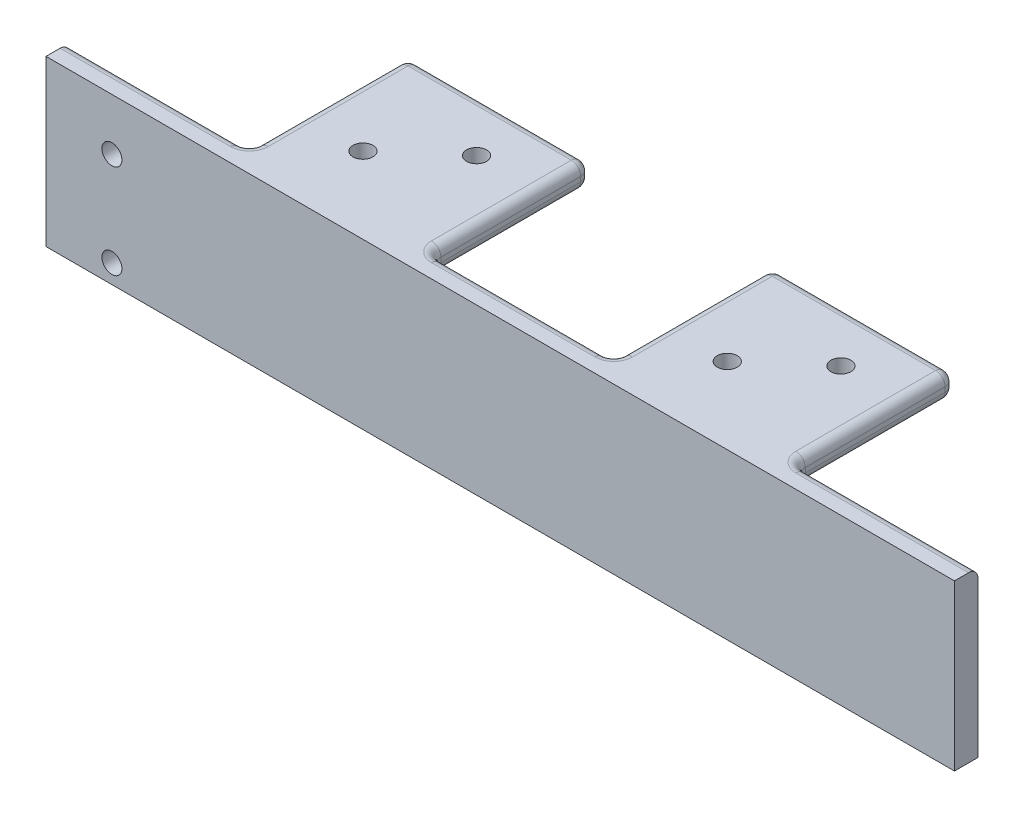
SolidWorks part; units mm, degrees
ref_plane "Front Plane" through (0, 0, 0) normal (0, 0, 1) x (1, 0, 0)
ref_plane "Top Plane" through (0, 0, 0) normal (0, 1, 0) x (1, 0, 0)
ref_plane "Right Plane" through (0, 0, 0) normal (1, 0, 0) x (0, 0, -1)
sketch "Sketch1" plane through (0, 0, 0) normal (0, 1, 0) x (1, 0, 0)
  line L1 (-96.5, 2.5) -> (96.5, 2.5)
  line L2 (-96.5, 2.5) -> (-96.5, -2.5)
  line L3 (-96.5, -2.5) -> (96.5, -2.5)
  line L4 (96.5, 2.5) -> (96.5, -2.5)
  line L5 (-96.5, 2.5) -> (96.5, -2.5) construction
  line L6 (-96.5, -2.5) -> (96.5, 2.5) construction
  point P0 (0, 0)
  dimension "D1" = 193
  dimension "D2" = 5
extrude "Boss-Extrude1" add sketch "Sketch1" along normal mid plane 30
sketch "Sketch2" plane through (0, 15, 0) normal (0, 1, 0) x (1, 0, 0)
  line L45 (96.5, 2.5) -> (-96.5, 2.5) construction
  line L46 (-58.3, 2.5) -> (-19.6, 2.5)
  line L47 (-58.3, 2.5) -> (-58.3, 36.2)
  line L48 (-58.3, 36.2) -> (-19.6, 36.2)
  line L49 (-19.6, 2.5) -> (-19.6, 36.2)
  line L51 (19.1, 36.2) -> (57.8, 36.2)
  line L52 (19.1, 2.5) -> (19.1, 36.2)
  line L53 (19.1, 2.5) -> (57.8, 2.5)
  line L54 (57.8, 2.5) -> (57.8, 36.2)
  line L55 (-58.3, 36.2) -> (-19.6, 36.2) construction
  line L60 (96.5, -2.5) -> (96.5, 2.5) construction
  dimension "D1" = 38.7
  dimension "D2" = 33.7
  dimension "D4" = 38.7
  dimension "D5" = 2
  dimension "D3" = 38.7
extrude "Boss-Extrude2" add sketch "Sketch2" along normal blind 5
sketch "Sketch3" plane through (0, 15, 0) normal (0, -1, 0) x (1, 0, 0)
  line L0 (-45.4, -13.73) -> (32, -13.73) construction
  line L4 (-19.6, -2.5) -> (-19.6, -36.2) construction
  line L6 (-19.6, -2.5) -> (-58.3, -2.5) construction
  line L7 (-58.3, -36.2) -> (-19.6, -36.2) construction
  circle A4 centre (-45.4, -13.73) radius 2.125
  circle A5 centre (-32.5, -24.97) radius 2.125
  circle A20 centre (32, -13.73) radius 2.125
  circle A21 centre (44.9, -24.97) radius 2.125
  dimension "D1" = 11.23
  dimension "D2" = 4.25
  dimension "D3" = 4.25
  dimension "D4" = 12.9
  dimension "D5" = 11.23
  dimension "D6" = 77.4
  dimension "D8" = 12.9
extrude "Cut-Extrude1" cut sketch "Sketch3" against normal up to next
fillet "Fillet3" radius 2 8 edges at (-19.6, 17.5, -2.5) (-58.3, 17.5, -2.5) (-58.3, 17.5, -36.2) (-19.6, 17.5, -36.2) (19.1, 17.5, -2.5) (19.1, 17.5, -36.2) (57.8, 17.5, -36.2) (57.8, 17.5, -2.5)
fillet "Fillet4" radius 2 31 edges at (-19.0142, 20, -3.0858) (-19.0142, 15, -3.0858) (-58.8858, 20, -3.0858) (-58.8858, 15, -3.0858) (-58.3, 15, -19.35) (-58.3, 20, -19.35) (-57.7142, 20, -35.6142) (-57.7142, 15, -35.6142) (-38.95, 15, -36.2) (-38.95, 20, -36.2) (-20.1858, 20, -35.6142) (-20.1858, 15, -35.6142) (78.15, 20, -2.5) (58.3858, 20, -3.0858) (58.3858, 15, -3.0858) (-78.4, 20, -2.5) (-19.6, 20, -19.35) (-19.6, 15, -19.35) (-0.25, 20, -2.5) (18.5142, 20, -3.0858) (18.5142, 15, -3.0858) (19.1, 15, -19.35) (19.1, 20, -19.35) (19.6858, 20, -35.6142) (19.6858, 15, -35.6142) (38.45, 15, -36.2) (38.45, 20, -36.2) (57.2142, 20, -35.6142) (57.2142, 15, -35.6142) (57.8, 15, -19.35) (57.8, 20, -19.35)
sketch "Sketch4" plane through (0, 0, 2.5) normal (0, 0, 1) x (1, 0, 0)
  line L1 (-96.5, 20) -> (-96.5, -15) construction
  line L2 (-96.5, -15) -> (96.5, -15) construction
  circle A0 centre (-82.5, 9) radius 2.125
  circle A1 centre (-82.5, -11) radius 2.125
  dimension "D3" = 4.25
  dimension "D6" = 4.25
  dimension "D1" = 20
  dimension "D2" = 14
  dimension "D4" = 14
  dimension "D5" = 4
extrude "Cut-Extrude2" cut sketch "Sketch4" against normal through all
